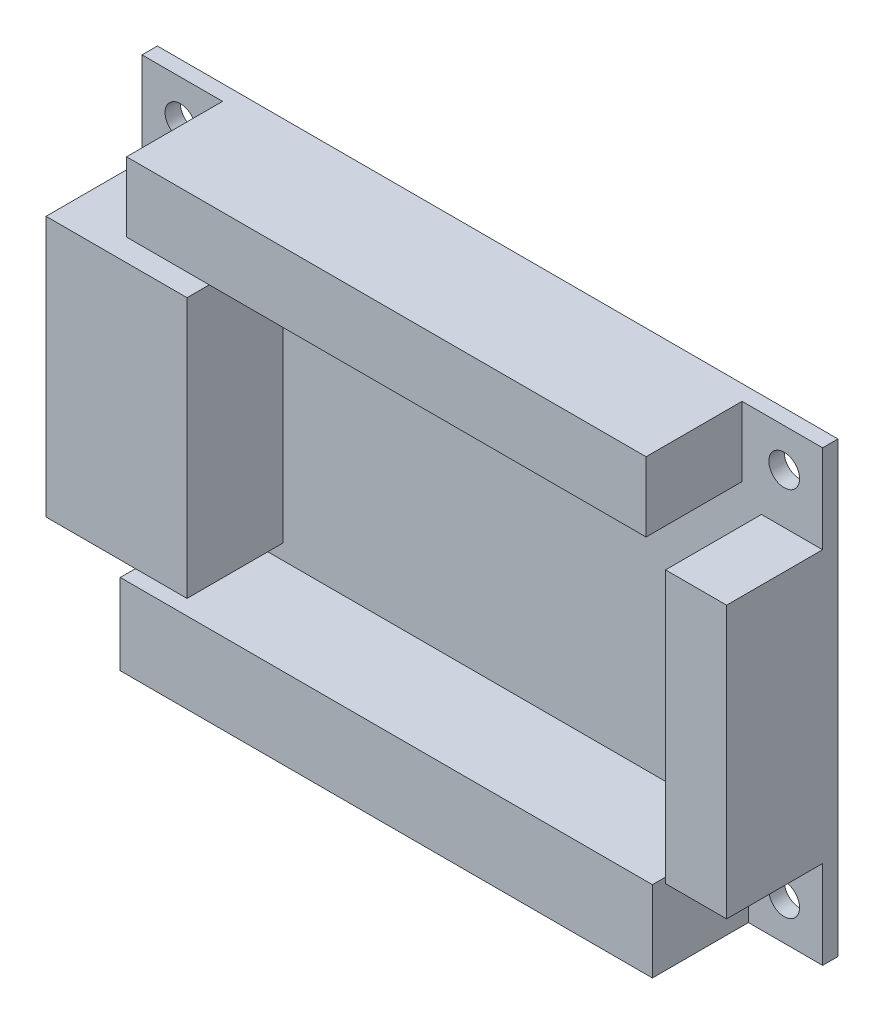
SolidWorks part; units mm, degrees
ref_plane "Plano frontal" through (0, 0, 0) normal (0, 0, 1) x (1, 0, 0)
ref_plane "Plano superior" through (0, 0, 0) normal (0, 1, 0) x (1, 0, 0)
ref_plane "Plano direito" through (0, 0, 0) normal (1, 0, 0) x (0, 0, -1)
sketch "Esboço1" plane through (0, 0, 0) normal (0, 0, 1) x (1, 0, 0)
  line L0 (-11.2515, 0) -> (0, 0) construction
  line L1 (-35.45, 23.35) -> (35.45, 23.35)
  line L2 (-35.45, 23.35) -> (-35.45, -23.35)
  line L3 (-35.45, -23.35) -> (35.45, -23.35)
  line L4 (35.45, 23.35) -> (35.45, -23.35)
  line L5 (-35.45, 23.35) -> (35.45, -23.35) construction
  line L6 (-35.45, -23.35) -> (35.45, 23.35) construction
  line L7 (0, 0) -> (0, 10.1302) construction
  circle A0 centre (-31.45, 19.35) radius 1.6
  circle A1 centre (31.45, 19.35) radius 1.6
  circle A2 centre (31.45, -19.35) radius 1.6
  circle A3 centre (-31.45, -19.35) radius 1.6
  point P0 (0, 0)
  dimension "D3" = 3.2
  dimension "D1" = 70.9
  dimension "D2" = 46.7
  dimension "D4" = 4
  dimension "D5" = 4
extrude "Ressalto-extrusão1" add sketch "Esboço1" along normal blind 1.6
sketch "Esboço2" plane through (0, 0, 1.6) normal (0, 0, 1) x (1, 0, 0)
  line L0 (35.45, 23.35) -> (-35.45, 23.35) construction
  line L5 (-35.45, -23.35) -> (35.45, -23.35) construction
  line L6 (-27.7202, -14.9303) -> (27.7202, -14.9303)
  line L7 (-27.0602, 16.1036) -> (27.0602, 16.1036)
  line L8 (-27.0602, 16.1036) -> (-27.0602, 23.35)
  line L9 (-27.0602, 23.35) -> (27.0602, 23.35)
  line L10 (27.0602, 16.1036) -> (27.0602, 23.35)
  line L11 (-27.0602, 16.1036) -> (27.0602, 23.35) construction
  line L12 (-27.0602, 23.35) -> (27.0602, 16.1036) construction
  line L13 (-27.7202, -14.9303) -> (-27.7202, -23.35)
  line L14 (-27.7202, -23.35) -> (27.7202, -23.35)
  line L15 (27.7202, -14.9303) -> (27.7202, -23.35)
  line L16 (-27.7202, -14.9303) -> (27.7202, -23.35) construction
  line L17 (-27.7202, -23.35) -> (27.7202, -14.9303) construction
  line L18 (35.45, -23.35) -> (35.45, 23.35) construction
  line L19 (29.0838, -14.1534) -> (35.45, -14.1534)
  line L20 (29.0838, -14.1534) -> (29.0838, 14.1534)
  line L21 (29.0838, 14.1534) -> (35.45, 14.1534)
  line L22 (35.45, -14.1534) -> (35.45, 14.1534)
  line L23 (29.0838, -14.1534) -> (35.45, 14.1534) construction
  line L24 (29.0838, 14.1534) -> (35.45, -14.1534) construction
  line L25 (-35.45, 23.35) -> (-35.45, -23.35) construction
  line L26 (-20.7632, -13.3468) -> (-35.45, -13.3468)
  line L27 (-20.7632, -13.3468) -> (-20.7632, 13.7871)
  line L28 (-20.7632, 13.7871) -> (-35.45, 13.7871)
  line L29 (-35.45, -13.3468) -> (-35.45, 13.7871)
  line L30 (-20.7632, -13.3468) -> (-35.45, 13.7871) construction
  line L31 (-20.7632, 13.7871) -> (-35.45, -13.3468) construction
  point P0 (0, -19.1401)
  point P6 (0, 19.7268)
  point P15 (32.2669, 0)
  point P22 (-28.1066, 0.2201)
  point P29 (-20.7632, 13.7871)
extrude "Ressalto-extrusão2" add sketch "Esboço2" along normal blind 10
equation "\"D5@Esboço1\"=\"D4@Esboço1\""
